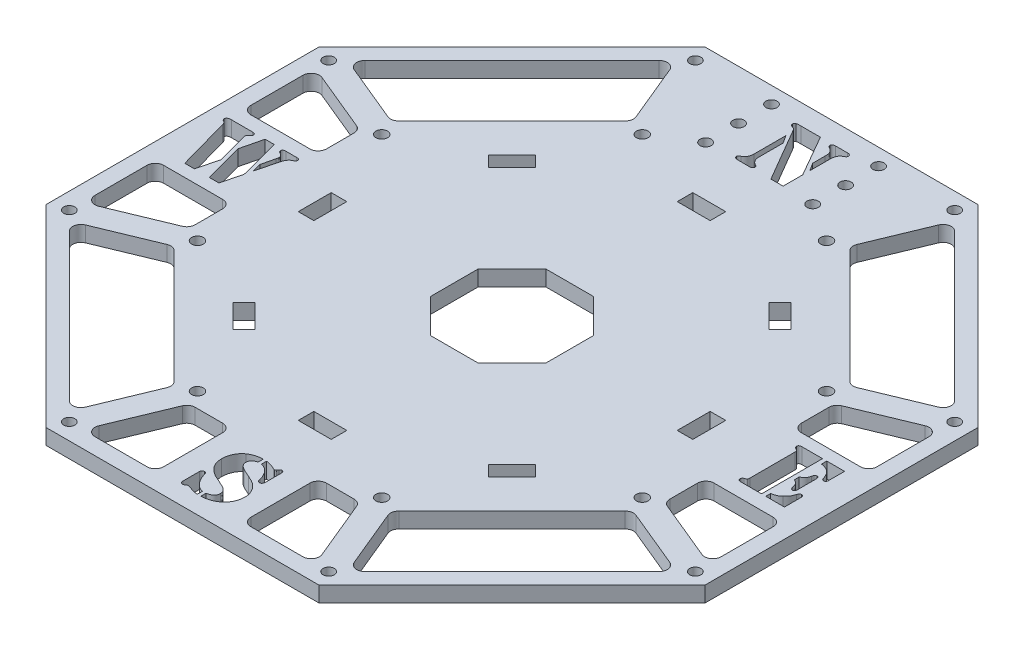
SolidWorks part; units mm, degrees
material "Custom Plastic"
ref_plane "Front Plane" through (0, 0, 0) normal (0, 0, 1) x (1, 0, 0)
ref_plane "Top Plane" through (0, 0, 0) normal (0, 1, 0) x (1, 0, 0)
ref_plane "Right Plane" through (0, 0, 0) normal (1, 0, 0) x (0, 0, -1)
ref_axis "Axis1" through (0, -0.2997, 0) along (0, 1, 0)
sketch "Base sketch" plane through (0, 0, 0) normal (0, 1, 0) x (1, 0, 0)
  line L1 (-127, 52.6051) -> (-127, -52.6051)
  line L2 (-127, -52.6051) -> (-52.6051, -127)
  line L3 (-52.6051, -127) -> (52.6051, -127)
  line L4 (52.6051, -127) -> (127, -52.6051)
  line L5 (127, -52.6051) -> (127, 52.6051)
  line L6 (127, 52.6051) -> (52.6051, 127)
  line L7 (52.6051, 127) -> (-52.6051, 127)
  line L8 (-52.6051, 127) -> (-127, 52.6051)
  circle A0 centre (0, 0) radius 127 construction
  dimension "D1" = 254
extrude "Base" add sketch "Base sketch" along normal blind 6
sketch "Sketch4" plane through (0, 6, 0) normal (0, 1, 0) x (1, 0, 0)
  line L0 (0, 0) -> (0, 127) construction
  line L1 (52.6051, 127) -> (-52.6051, 127) construction
  line L4 (-6.35, 70.025) -> (6.35, 70.025)
  line L5 (-6.35, 70.025) -> (-6.35, 76.025)
  line L6 (-6.35, 76.025) -> (6.35, 76.025)
  line L7 (6.35, 70.025) -> (6.35, 76.025)
  line L8 (-6.35, 70.025) -> (6.35, 76.025) construction
  line L10 (-6.35, 76.025) -> (6.35, 70.025) construction
  point P5 (0, 73.025)
  dimension "D1" = 6
  dimension "D2" = 12.7
  dimension "D3" = 53.975
extrude "Support cutouts" cut sketch "Sketch4" against normal up to next
pattern_circular "Support cutout pattern" count 8 over 360 about axis through (0, -0.2997, 0) along (0, 1, 0) of "Support cutouts"
sketch "Sketch11" plane through (0, 6, 0) normal (0, 1, 0) x (1, 0, 0)
  line L1 (92.075, 38.1387) -> (38.1387, 92.075) construction
  line L2 (38.1387, 92.075) -> (-38.1387, 92.075) construction
  line L3 (-38.1387, 92.075) -> (-92.075, 38.1387) construction
  line L4 (-92.075, 38.1387) -> (-92.075, -38.1387) construction
  line L5 (-92.075, -38.1387) -> (-38.1387, -92.075) construction
  line L6 (-38.1387, -92.075) -> (38.1387, -92.075) construction
  line L7 (38.1387, -92.075) -> (92.075, -38.1387) construction
  line L8 (92.075, -38.1387) -> (92.075, 38.1387) construction
  line L9 (-35.5085, 85.725) -> (-85.725, 35.5085)
  line L10 (-85.725, 35.5085) -> (-85.725, -35.5085)
  line L11 (-85.725, -35.5085) -> (-35.5085, -85.725)
  line L12 (-35.5085, -85.725) -> (35.5085, -85.725)
  line L13 (35.5085, -85.725) -> (85.725, -35.5085)
  line L14 (85.725, -35.5085) -> (85.725, 35.5085)
  line L15 (85.725, 35.5085) -> (35.5085, 85.725)
  line L16 (35.5085, 85.725) -> (-35.5085, 85.725)
  circle A0 centre (0, 0) radius 92.075 construction
  circle A1 centre (0, 0) radius 85.725 construction
  dimension "D1" = 184.15
  dimension "D2" = 6.35
hole_wizard "#8 Clearance Hole1" positions "Sketch13" profile "Sketch12" hole size "#8" standard "ANSI Inch" end condition through all
sketch "Sketch13" plane through (0, 6, 0) normal (0, 1, 0) x (1, 0, 0)
  point P0 (-85.725, 35.5085)
  point P3 (-35.5085, 85.725)
  point P6 (35.5085, 85.725)
  point P9 (85.725, 35.5085)
  point P12 (85.725, -35.5085)
  point P15 (35.5085, -85.725)
  point P18 (-35.5085, -85.725)
  point P21 (-85.725, -35.5085)
sketch "Sketch12" plane through (-85.725, 6, -35.5085) normal (1, 0, 0) x (0, 0, 1)
  line L0 (0, 0) -> (0, 6)
  line L1 (0, 6) -> (2.2479, 6)
  line L2 (2.2479, 6) -> (2.2479, 0)
  line L5 (2.2479, 0) -> (0, 0)
  line L11 (0, -6.35) -> (0, 107.95) construction
  dimension "Thru Hole Dia." = 4.4958
  dimension "Thru Hole Depth" = 6
sketch "Sketch29" plane through (0, 6, 0) normal (0, 1, 0) x (1, 0, 0)
  line L0 (-6.35, 70.025) -> (6.35, 70.025) construction
  line L1 (-22.225, -9.2059) -> (-9.2059, -22.225)
  line L2 (-9.2059, -22.225) -> (9.2059, -22.225)
  line L3 (9.2059, -22.225) -> (22.225, -9.2059)
  line L4 (22.225, -9.2059) -> (22.225, 9.2059)
  line L5 (22.225, 9.2059) -> (9.2059, 22.225)
  line L6 (9.2059, 22.225) -> (-9.2059, 22.225)
  line L7 (-9.2059, 22.225) -> (-22.225, 9.2059)
  line L8 (-22.225, 9.2059) -> (-22.225, -9.2059)
  circle A0 centre (0, 0) radius 22.225 construction
  dimension "D1" = 44.45
extrude "Motor wire holes" cut sketch "Sketch29" against normal through all
sketch "mount sketch" plane through (0, 6, 0) normal (0, 1, 0) x (1, 0, 0)
  line L0 (52.6051, 127) -> (-52.6051, 127) construction
  line L1 (49.9749, 120.65) -> (-49.9749, 120.65) construction
  line L2 (-49.9749, 120.65) -> (-120.65, 49.9749) construction
  line L3 (-120.65, 49.9749) -> (-120.65, -49.9749) construction
  line L4 (-120.65, -49.9749) -> (-49.9749, -120.65) construction
  line L5 (-49.9749, -120.65) -> (49.9749, -120.65) construction
  line L6 (49.9749, -120.65) -> (120.65, -49.9749) construction
  line L7 (120.65, -49.9749) -> (120.65, 49.9749) construction
  line L8 (120.65, 49.9749) -> (49.9749, 120.65) construction
  circle A0 centre (0, 0) radius 120.65 construction
  dimension "D1" = 6.35
hole_wizard "mount clearance holes" positions "Sketch32" profile "Sketch31" hole size "#8" standard "ANSI Inch"
sketch "Sketch32" plane through (0, 6, 0) normal (0, 1, 0) x (1, 0, 0)
  point P0 (-120.65, 49.9749)
  point P3 (-49.9749, 120.65)
  point P6 (49.9749, 120.65)
  point P9 (120.65, 49.9749)
  point P12 (120.65, -49.9749)
  point P15 (49.9749, -120.65)
  point P18 (-49.9749, -120.65)
  point P21 (-120.65, -49.9749)
sketch "Sketch31" plane through (-120.65, 6, -49.9749) normal (1, 0, 0) x (0, 0, 1)
  line L0 (0, 0) -> (0, 6.35)
  line L1 (0, 6.35) -> (2.1526, 6.35)
  line L2 (2.1526, 6.35) -> (2.1526, 0)
  line L5 (2.1526, 0) -> (0, 0)
  line L10 (0, 6.35) -> (-2.1526, 6.35) construction
  line L11 (0, -6.35) -> (0, 107.95) construction
  dimension "Hole Dia." = 4.3053
  dimension "Hole Depth" = 6.35
  dimension "Drill Angle" = 180
sketch "Sketch33" plane through (0, 6, 0) normal (0, 1, 0) x (1, 0, 0)
  line L0 (0, 0) -> (0, 95.25) construction
  line L1 (127, -52.6051) -> (127, 52.6051) construction
  line L2 (-20.6375, 120.65) -> (20.6375, 120.65) construction
  line L3 (0, 95.25) -> (0, 107.95) construction
  line L4 (-20.6375, 107.95) -> (20.6375, 107.95) construction
  line L5 (0, 107.95) -> (0, 120.65) construction
  line L6 (-20.6375, 95.25) -> (20.6375, 95.25) construction
  line L7 (52.6051, 127) -> (-52.6051, 127) construction
  line L9 (20.6375, 95.25) -> (20.6375, 107.95) construction
  line L10 (20.6375, 107.95) -> (20.6375, 120.65) construction
  line L11 (-20.6375, 95.25) -> (-20.6375, 107.95) construction
  line L12 (-20.6375, 107.95) -> (-20.6375, 120.65) construction
  dimension "D1" = 6.35
  dimension "D2" = 12.7
  dimension "D3" = 41.275
hole_wizard "#8 Clearance Hole2" positions "Sketch35" profile "Sketch34" hole size "#8" standard "ANSI Inch" end condition through all
sketch "Sketch35" plane through (0, 6, 0) normal (0, 1, 0) x (1, 0, 0)
  point P0 (20.6375, 95.25)
  point P3 (20.6375, 107.95)
  point P6 (20.6375, 120.65)
  point P9 (-20.6375, 120.65)
  point P12 (-20.6375, 107.95)
  point P15 (-20.6375, 95.25)
sketch "Sketch34" plane through (20.6375, 6, -95.25) normal (1, 0, 0) x (0, 0, 1)
  line L0 (0, 0) -> (0, 6)
  line L1 (0, 6) -> (2.1526, 6)
  line L2 (2.1526, 6) -> (2.1526, 0)
  line L5 (2.1526, 0) -> (0, 0)
  line L11 (0, -6.35) -> (0, 107.95) construction
  dimension "Thru Hole Dia." = 4.3053
  dimension "Thru Hole Depth" = 6
sketch "Sketch36" plane through (0, 6, 0) normal (0, 1, 0) x (1, 0, 0)
  line L0 (-15.7154, 15.7154) -> (-89.8026, 89.8026) construction
  line L1 (-9.2059, 22.225) -> (-22.225, 9.2059) construction
  line L2 (-52.6051, 127) -> (-127, 52.6051) construction
  line L3 (-112.6149, 51.8015) -> (-90.3899, 42.5956)
  line L4 (-86.9298, 43.2839) -> (-43.2839, 86.9298)
  line L5 (-113.645, 56.9799) -> (-56.9799, 113.645)
  line L6 (-120.65, 49.9749) -> (-85.725, 35.5085) construction
  line L7 (-51.8015, 112.6149) -> (-42.5956, 90.3899)
  line L8 (56.9799, 113.645) -> (113.645, 56.9799)
  line L9 (112.6149, 51.8015) -> (90.3899, 42.5956)
  line L10 (43.2839, 86.9298) -> (86.9298, 43.2839)
  line L11 (51.8015, 112.6149) -> (42.5956, 90.3899)
  line L12 (113.645, -56.9799) -> (56.9799, -113.645)
  line L13 (51.8015, -112.6149) -> (42.5956, -90.3899)
  line L14 (86.9298, -43.2839) -> (43.2839, -86.9298)
  line L15 (112.6149, -51.8015) -> (90.3899, -42.5956)
  line L16 (-56.9799, -113.645) -> (-113.645, -56.9799)
  line L17 (-112.6149, -51.8015) -> (-90.3899, -42.5956)
  line L18 (-43.2839, -86.9298) -> (-86.9298, -43.2839)
  line L19 (-51.8015, -112.6149) -> (-42.5956, -90.3899)
  line L20 (127, 52.6051) -> (52.6051, 127) construction
  line L21 (0, 0) -> (65.1069, 65.1069) construction
  line L22 (-15.7154, 15.7154) -> (0, 0) construction
  circle A1 centre (-85.725, 35.5085) radius 2.2479 construction
  arc A2 (-112.6149, 51.8015) -> (-113.645, 56.9799) centre (-111.3999, 54.7348) cw
  arc A3 (-90.3899, 42.5956) -> (-86.9298, 43.2839) centre (-89.1749, 45.5289) ccw
  arc A4 (-42.5956, 90.3899) -> (-43.2839, 86.9298) centre (-45.5289, 89.1749) cw
  arc A5 (-51.8015, 112.6149) -> (-56.9799, 113.645) centre (-54.7348, 111.3999) ccw
  arc A6 (112.6149, 51.8015) -> (113.645, 56.9799) centre (111.3999, 54.7348) ccw
  arc A7 (90.3899, 42.5956) -> (86.9298, 43.2839) centre (89.1749, 45.5289) cw
  arc A8 (42.5956, 90.3899) -> (43.2839, 86.9298) centre (45.5289, 89.1749) ccw
  arc A9 (51.8015, 112.6149) -> (56.9799, 113.645) centre (54.7348, 111.3999) cw
  arc A10 (51.8015, -112.6149) -> (56.9799, -113.645) centre (54.7348, -111.3999) ccw
  arc A11 (42.5956, -90.3899) -> (43.2839, -86.9298) centre (45.5289, -89.1749) cw
  arc A12 (90.3899, -42.5956) -> (86.9298, -43.2839) centre (89.1749, -45.5289) ccw
  arc A13 (112.6149, -51.8015) -> (113.645, -56.9799) centre (111.3999, -54.7348) cw
  arc A14 (-112.6149, -51.8015) -> (-113.645, -56.9799) centre (-111.3999, -54.7348) ccw
  arc A15 (-90.3899, -42.5956) -> (-86.9298, -43.2839) centre (-89.1749, -45.5289) cw
  arc A16 (-42.5956, -90.3899) -> (-43.2839, -86.9298) centre (-45.5289, -89.1749) ccw
  arc A17 (-51.8015, -112.6149) -> (-56.9799, -113.645) centre (-54.7348, -111.3999) cw
  point P17 (-85.3124, 85.3124)
  point P18 (-65.1069, 65.1069)
  point P20 (-117.0049, 53.6199)
  point P23 (-88.4299, 41.7838)
  point P26 (-41.7838, 88.4299)
  point P29 (-53.6199, 117.0049)
  point P69 (0, 0)
  dimension "D2" = 6.35
  dimension "D4" = 3.175
  dimension "D1" = 6.35
  dimension "D3" = 9.525
  dimension "D6" = 6.35
  dimension "D5" = 4
extrude "Lightenning 1" cut sketch "Sketch36" against normal through all
sketch "Sketch37" plane through (0, 6, 0) normal (0, 1, 0) x (1, 0, 0)
  text T0 "N" font "Stencil" height in points 100
  text T1 "S" font "Stencil" height in points 100
  text T2 "E" font "Stencil" height in points 100
  text T3 "W" font "Stencil" height in points 100
extrude "Directions" cut sketch "Sketch37" against normal through all
sketch "Sketch38" plane through (0, 6, 0) normal (0, 1, 0) x (1, 0, 0)
  line L0 (120.65, 40.0683) -> (120.65, 20.0025)
  line L1 (117.475, 16.8275) -> (94.7002, 16.8275)
  line L2 (91.5252, 20.0025) -> (91.5252, 30.6346)
  line L3 (93.4852, 33.5679) -> (116.26, 43.0016)
  line L4 (85.725, 35.5085) -> (120.65, 49.9749) construction
  line L5 (0, 0) -> (127, 0) construction
  line L6 (127, -52.6051) -> (127, 52.6051) construction
  line L7 (101.5024, 47.1986) -> (103.1875, 42.7417) construction
  line L8 (90.3899, 42.5956) -> (112.6149, 51.8015) construction
  line L9 (103.1875, 42.7417) -> (104.8726, 38.2848) construction
  line L10 (113.645, 56.9799) -> (120.65, 49.9749) construction
  line L11 (120.65, 49.9749) -> (120.65, 44.82) construction
  line L12 (113.645, 56.9799) -> (56.9799, 113.645) construction
  line L14 (117.475, -16.8275) -> (94.7002, -16.8275)
  line L15 (120.65, -40.0683) -> (120.65, -20.0025)
  line L16 (93.4852, -33.5679) -> (116.26, -43.0016)
  line L17 (91.5252, -20.0025) -> (91.5252, -30.6346)
  arc A0 (117.475, -16.8275) -> (120.65, -20.0025) centre (117.475, -20.0025) cw
  arc A1 (94.7002, -16.8275) -> (91.5252, -20.0025) centre (94.7002, -20.0025) ccw
  arc A2 (93.4852, -33.5679) -> (91.5252, -30.6346) centre (94.7002, -30.6346) cw
  arc A3 (120.65, -40.0683) -> (116.26, -43.0016) centre (117.475, -40.0683) cw
  arc A4 (120.65, 20.0025) -> (117.475, 16.8275) centre (117.475, 20.0025) cw
  arc A5 (94.7002, 16.8275) -> (91.5252, 20.0025) centre (94.7002, 20.0025) cw
  arc A6 (91.5252, 30.6346) -> (93.4852, 33.5679) centre (94.7002, 30.6346) cw
  arc A7 (120.65, 40.0683) -> (116.26, 43.0016) centre (117.475, 40.0683) ccw
  arc A8 (112.6149, 51.8015) -> (113.645, 56.9799) centre (111.3999, 54.7348) ccw construction
  point P28 (120.65, -16.8275)
  point P31 (91.5252, -16.8275)
  point P34 (91.5252, -32.7561)
  point P37 (120.65, -44.82)
  point P40 (120.65, 16.8275)
  point P43 (91.5252, 16.8275)
  point P46 (91.5252, 32.7561)
  dimension "D1" = 33.655
extrude "Lightenning 2" cut sketch "Sketch38" against normal through all
pattern_circular "Lightenning 2 circ pat" count 3 every 90 about axis through (0, -0.2997, 0) along (0, 1, 0) of "Lightenning 2" reverse direction yes
equation "\"MAT_THICKNESS\"=0.23622"
equation "\"D1@Base\"=\"MAT_THICKNESS\""
equation "\"D1@Sketch4\"=\"MAT_THICKNESS\""
